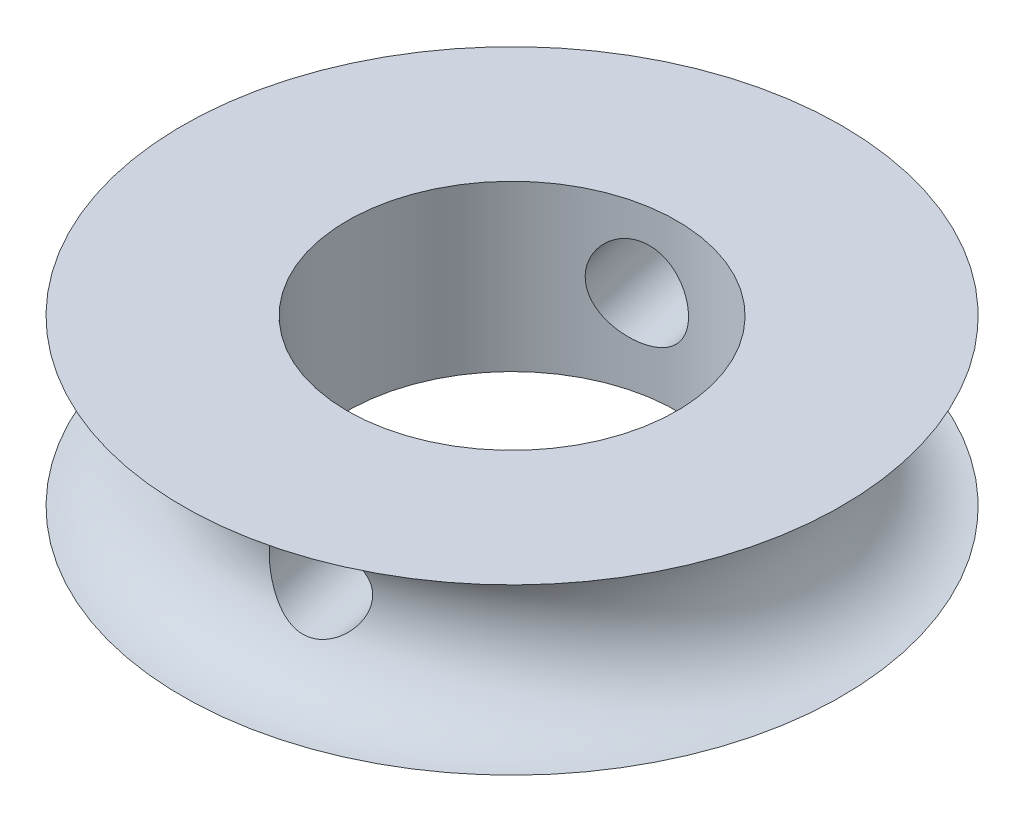
SolidWorks part; units mm, degrees
ref_plane "Front Plane" through (0, 0, 0) normal (0, 0, 1) x (1, 0, 0)
ref_plane "Top Plane" through (0, 0, 0) normal (0, 1, 0) x (1, 0, 0)
ref_plane "Right Plane" through (0, 0, 0) normal (1, 0, 0) x (0, 0, -1)
sketch "Sketch9" plane through (0, 0, 0) normal (0, 0, 1) x (1, 0, 0)
  line L1 (2.2969, -2.9354) -> (8.2969, -2.9354)
  line L3 (2.2969, 0.0646) -> (8.2969, 0.0646)
  line L4 (8.2969, -2.9354) -> (8.2969, 0.0646)
  arc A2 (2.2969, 0.0646) -> (2.2969, -2.9354) centre (2.2969, -1.4354) cw
  dimension "D1" = 3
  dimension "D2" = 6
revolve "Revolve1" add sketch "Sketch9" angle 360 about L4
sketch "Sketch117" plane through (0, 0.0646, 0) normal (0, 1, 0) x (1, 0, 0)
  circle A0 centre (8.2969, 0) radius 3
  point P2 (8.2386, 0)
  point P3 (8.2969, -0.5316)
  point P4 (0, 0)
  point P5 (8.3567, 0)
  point P6 (0, 0)
extrude "Cut-Extrude4" cut sketch "Sketch117" against normal blind 3
hole_wizard "M2x0.4 Tapped Hole1" positions "3DSketch2" profile "Sketch118" tap size "M2x0.4" standard "ANSI Metric" end condition through all
sketch3d "3DSketch2"
  point P0 (9.1753, -1.4181, 4.4135)
  point P2 (10.6992, 2.4247, 0)
cosmetic thread "Hole Thread1" parameters "D2"=2
sketch "Sketch118" plane through (9.1753, -1.4181, 4.4135) normal (0.701, 0.701, -0.1313) x (0.6859, -0.7131, -0.1449)
  line L0 (0, 0) -> (0, 11.5722)
  line L1 (0, 11.5722) -> (0.8, 11.5722)
  line L2 (0.8, 11.5722) -> (0.8, 0)
  line L5 (0.8, 0) -> (0, 0)
  line L11 (0, -6.35) -> (0, 107.95) construction
  dimension "Thru Tap Drill Dia." = 1.6
  dimension "Thru Tap Drill Depth" = 11.5722
